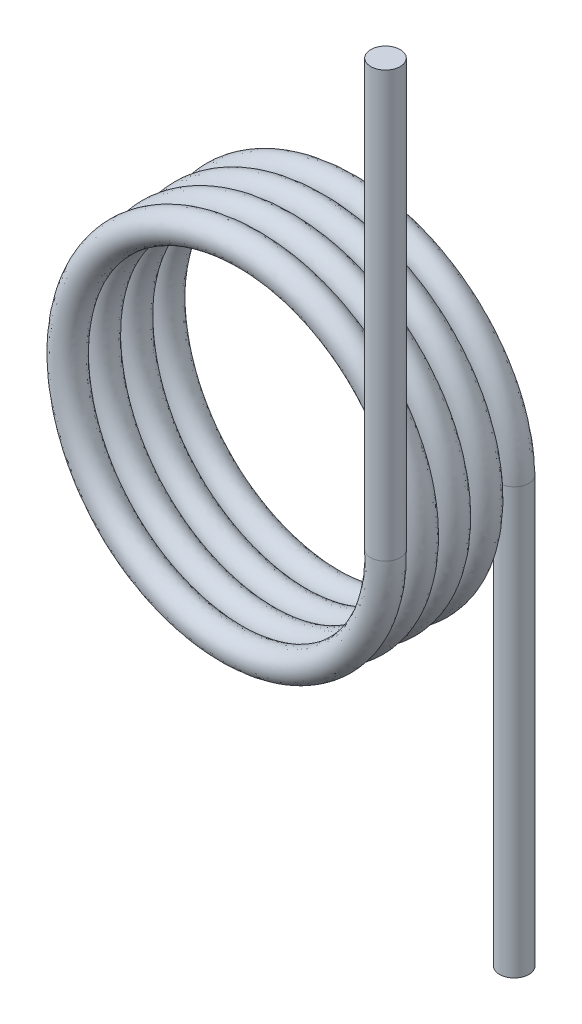
SolidWorks part; units mm, degrees
note: '?' marks a value the reader was unsure of.
ref_plane "Front" through (0, 0, 0) normal (0, 0, 1) x (1, 0, 0)
ref_plane "Top" through (0, 0, 0) normal (0, 1, 0) x (1, 0, 0)
ref_plane "Right" through (0, 0, 0) normal (1, 0, 0) x (0, 0, -1)
sketch "Sketch1" plane through (0, 0, 0) normal (0, 0, 1) x (1, 0, 0)
  circle A0 centre (0, 0) radius 2.55
  circle A1 centre (0, 0) radius 2.25 construction
  circle A2 centre (0, 2.55) radius 0.3 construction
  dimension "D1" = 0.6
  dimension "D2" = 4.5
curve "Helix/Spiral1" pitch 0.4917 height 1.9667 turns 4
sketch "Sketch2" plane through (0, 0, 0) normal (0, 1, 0) x (1, 0, 0)
  circle A0 centre (2.55, 0) radius 0.225
  dimension "D1" = 0.45
sweep "Sweep1" add profiles "Sketch2" path "Helix/Spiral1"
sketch "Sketch4" plane through (0, 0, 0) normal (0, -1, 0) x (1, 0, 0)
  circle A1 centre (2.55, -1.9667) radius 0.225
  circle A2 centre (2.55, -1.9667) radius 0.225
  dimension "D1" = 0
extrude "Boss-Extrude1" add sketch "Sketch4" along normal blind 6.5
sketch "Sketch5" plane through (0, 0, 0) normal (0, 1, 0) x (1, 0, 0)
  circle A1 centre (2.55, 0) radius 0.225
  circle A2 centre (2.55, 0) radius 0.225
  dimension "D1" = 0
extrude "Boss-Extrude2" add sketch "Sketch5" along normal blind 6.5
sketch "Sketch11" plane through (0, 0, 0) normal (1, 0, 0) x (0, 0, -1)
  line L0 (0, 0) -> (1.9667, 0)
  line L2 (0.9833, 0) -> (0.9833, 5.2574)
  line L3 (1.9667, 2.55) -> (1.9667, 0) construction
  line L4 (2.1917, 0) -> (1.7417, 0) construction
ref_plane "Plane1" through (0, 0, -0.9833) normal (0, 0, 1) x (1, 0, 0)
ref_axis "Axis1" through (2.55, 10.4349, 0) along (0, -1, 0)?
ref_axis "Axis3" through (2.55, -0.815, -1.9667) along (0, -1, 0)?
